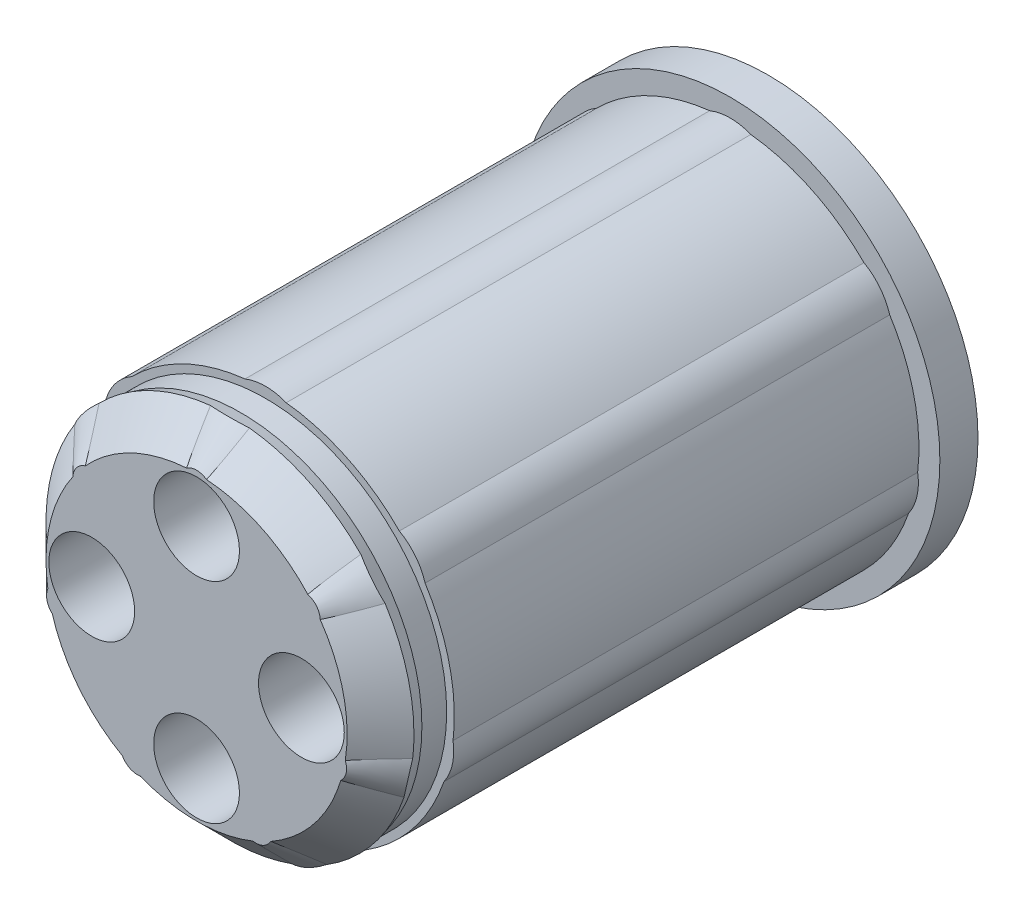
SolidWorks part; units mm, degrees
ref_plane "Ebene vorne" through (0, 0, 0) normal (0, 0, 1) x (1, 0, 0)
ref_plane "Ebene oben" through (0, 0, 0) normal (0, 1, 0) x (1, 0, 0)
ref_plane "Ebene rechts" through (0, 0, 0) normal (1, 0, 0) x (0, 0, -1)
sketch "Skizze1" plane through (0, 0, 0) normal (0, 0, 1) x (1, 0, 0)
  line L0 (0, 0) -> (0, 7.15) construction
  circle A0 centre (0, 0) radius 9.9
  circle A1 centre (0, 0) radius 10.05 construction
  circle A2 centre (0, 7.15) radius 2.9
  circle A7 centre (5.5901, 4.458) radius 2.9
  circle A8 centre (6.9707, -1.591) radius 2.9
  circle A9 centre (3.1023, -6.4419) radius 2.9
  circle A10 centre (-3.1023, -6.4419) radius 2.9
  circle A11 centre (-6.9707, -1.591) radius 2.9
  circle A12 centre (-5.5901, 4.458) radius 2.9
  point P17 (0, 0)
  point P21 (0, 0)
  dimension "D1" = 19.8
  dimension "D2" = 20.1
  dimension "D3" = 5.8
  dimension "D4" = 7
extrude "Aufsatz-Linear austragen1" add sketch "Skizze1" along normal blind 30 contours A0 A12 | A0 A2 | A0 A7 | A0 A8 | A0 A9 | A0 A10 | A0 A11 | A0 A11 | A0 A12 | A0 A2 | A0 A8 | A0 A9 | A0 A10 | A12 A0 A11 A10 A9 A8 A7 A2 | A0 A7 region at (0, 0, 0) region at (5.5718, 4.4434, 0) region at (7.7779, 6.2027, 0) region at (9.6989, -2.2137, 0) region at (6.948, -1.5858, 0) region at (0, 7.1267, 0) region at (0, 9.9483, 0) region at (4.3164, -8.9631, 0) region at (3.0921, -6.4209, 0) region at (-5.5718, 4.4434, 0) region at (-7.7779, 6.2027, 0) region at (-4.3164, -8.9631, 0) region at (-3.0921, -6.4209, 0) region at (-6.948, -1.5858, 0) region at (-9.6989, -2.2137, 0)
sketch "Skizze2" plane through (0, 0, 0) normal (0, 0, 1) x (1, 0, 0)
  circle A0 centre (0, 0) radius 11
  dimension "D1" = 22
extrude "Aufsatz-Linear austragen2" add sketch "Skizze2" along normal blind 2
chamfer "Fase1" distance 2 angle 45 14 edges at (9.798, -2.2363, 30) (7.7401, -6.1725, 30) (4.3605, -9.0547, 30) (0, -9.9, 30) (-4.3605, -9.0547, 30) (-7.7401, -6.1725, 30) (-9.798, -2.2363, 30) (-9.6518, 2.203, 30) (-7.8574, 6.2661, 30) (-4.2954, 8.9196, 30) (0, 10.05, 30) (4.2954, 8.9196, 30) (7.8574, 6.2661, 30) (9.6518, 2.203, 30)
sketch "Skizze3" plane through (0, 0, 2) normal (0, 0, 1) x (1, 0, 0)
  line L0 (0, 0) -> (0, 5.5) construction
  circle A0 centre (0, 0) radius 5.5 construction
  circle A1 centre (0, 5.5) radius 2.25
  circle A2 centre (5.5, 0) radius 2.25
  circle A3 centre (0, -5.5) radius 2.25
  circle A4 centre (-5.5, 0) radius 2.25
  point P14 (0, 0)
  dimension "D1" = 5.5
  dimension "D2" = 4.5
  dimension "D3" = 4
extrude "Schnitt-Linear austragen1" cut sketch "Skizze3" against normal through all and the other way through all
sketch "Skizze4" plane through (0, 0, 0) normal (1, 0, 0) x (0, 0, -1)
  line L0 (-2, 10.05) -> (-28, 10.05) construction
  line L1 (-27.6766, 10.05) -> (-26.3766, 10.05)
  line L2 (-27.6766, 10.05) -> (-27.6766, 9.5) construction
  line L3 (-27.6766, 9.5) -> (-26.3766, 9.5)
  line L4 (-26.3766, 10.05) -> (-26.3766, 9.5)
  line L5 (-27.6766, 9.5) -> (-29.7292, 10.05)
  line L6 (0, 0) -> (3.3435, 0) construction
  line L7 (-26.1766, 11.225) -> (-26.1766, -11.225) construction
  line L10 (-29.7292, 10.05) -> (-27.6766, 10.05)
  dimension "D1" = 0.2
  dimension "D2" = 19
  dimension "D3" = 1.3
  dimension "D4" = 75
revolve "Schnitt-Rotation1" cut sketch "Skizze4" angle 360 about L6
ref_axis "Achse1" through (0, 0, -1.5) along (0, 0, 1)
